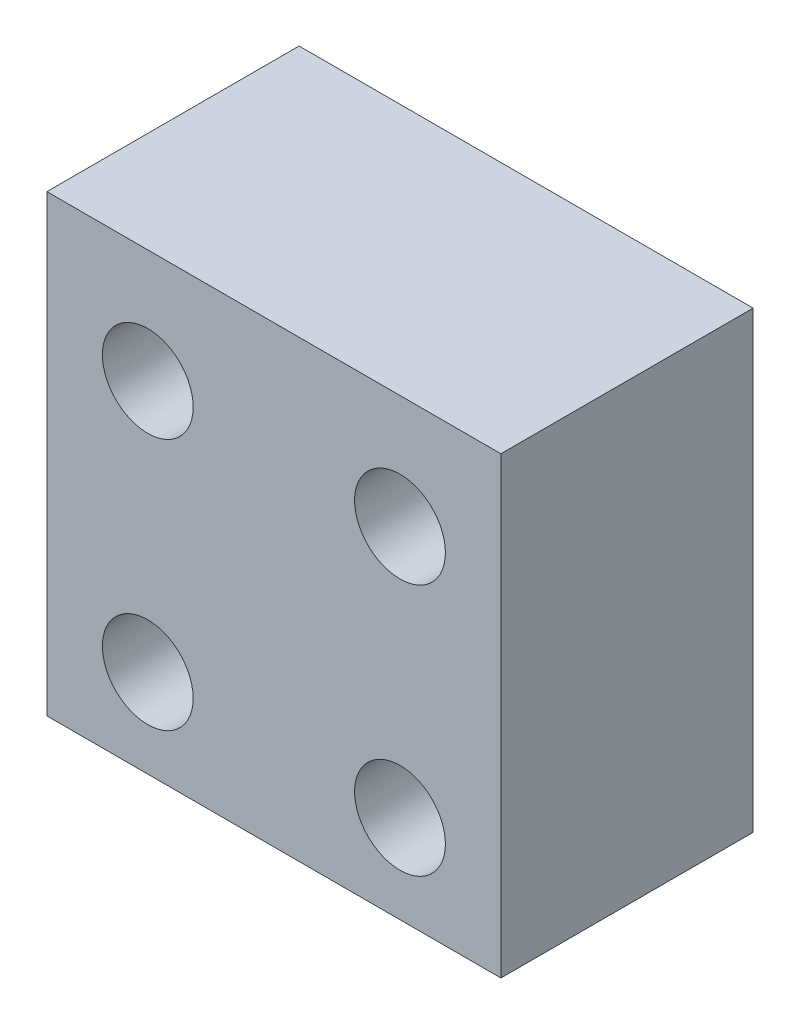
SolidWorks part; units mm, degrees
ref_plane "Front Plane" through (0, 0, 0) normal (0, 0, 1) x (1, 0, 0)
ref_plane "Top Plane" through (0, 0, 0) normal (0, 1, 0) x (1, 0, 0)
ref_plane "Right Plane" through (0, 0, 0) normal (1, 0, 0) x (0, 0, -1)
sketch "Sketch1" plane through (0, 0, 0) normal (0, 0, 1) x (1, 0, 0)
  line L0 (169, 104.999) -> (151, 104.999)
  line L8 (169, 86.999) -> (169, 104.999)
  line L10 (151, 104.999) -> (151, 86.999)
  line L11 (151, 86.999) -> (169, 86.999)
  dimension "D2" = 18
extrude "Boss-Extrude1" add sketch "Sketch1" along normal blind 10
sketch "Sketch2" plane through (0, 0, 10) normal (0, 0, 1) x (1, 0, 0)
  point P0 (165, 90.499)
  point P3 (155, 90.499)
  point P6 (155, 100.499)
  point P9 (165, 100.499)
hole_wizard "M3 Clearance Hole1" positions "Sketch2" profile "Sketch3" hole size "M3" standard "ANSI Metric" end condition through all
sketch "Sketch3" plane through (165, 90.499, 10) normal (1, 0, 0) x (0, -1, 0)
  line L0 (0, 0) -> (0, 10)
  line L1 (0, 10) -> (1.8, 10)
  line L2 (1.8, 10) -> (1.8, 0)
  line L5 (1.8, 0) -> (0, 0)
  line L11 (0, -6.35) -> (0, 107.95) construction
  dimension "Thru Hole Dia." = 3.6
  dimension "Thru Hole Depth" = 10
